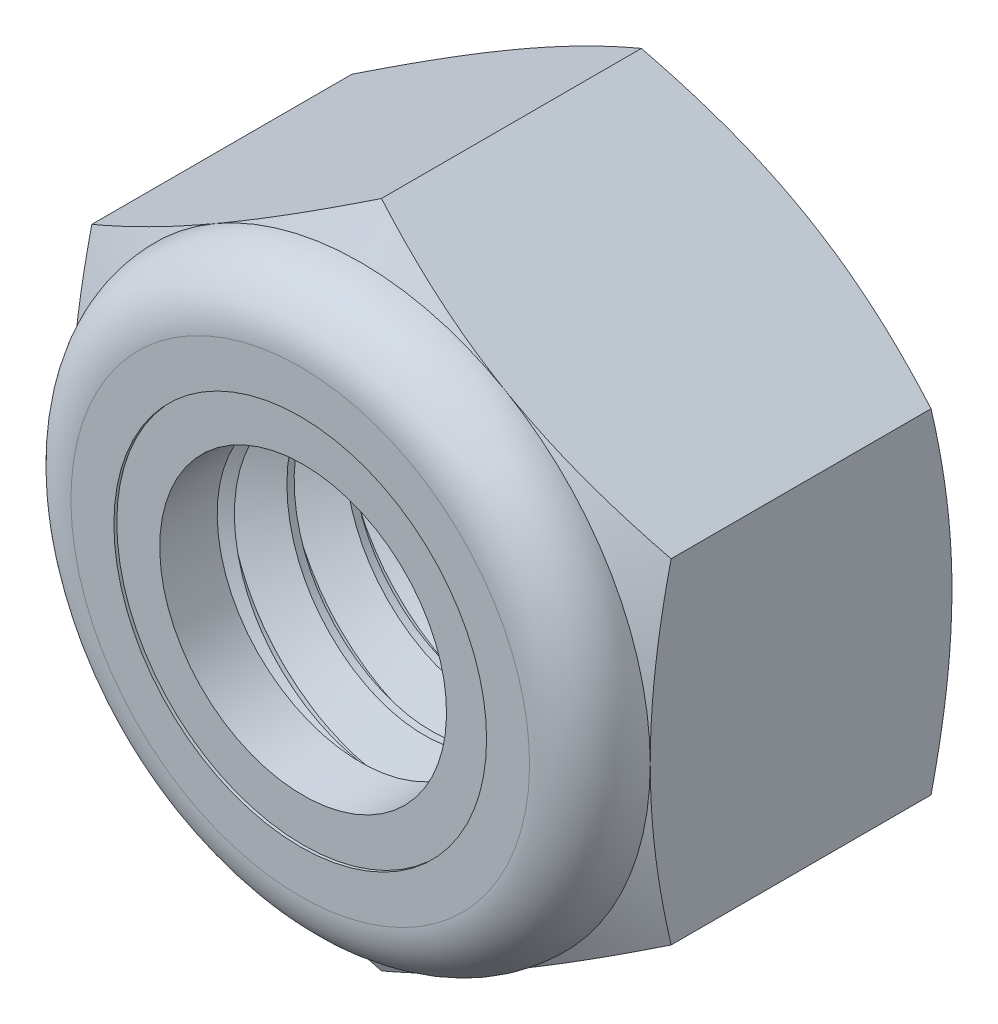
SolidWorks part; units mm, degrees
material "Cast Alloy Steel"
ref_plane "Front Plane" through (0, 0, 0) normal (0, 0, 1) x (1, 0, 0)
ref_plane "Top Plane" through (0, 0, 0) normal (0, 1, 0) x (1, 0, 0)
ref_plane "Right Plane" through (0, 0, 0) normal (1, 0, 0) x (0, 0, -1)
sketch "Sketch1" plane through (0, 0, 0) normal (0, 0, 1) x (1, 0, 0)
  line L1 (0, 4.6188) -> (-4, 2.3094)
  line L2 (-4, 2.3094) -> (-4, -2.3094)
  line L3 (-4, -2.3094) -> (0, -4.6188)
  line L4 (0, -4.6188) -> (4, -2.3094)
  line L5 (4, -2.3094) -> (4, 2.3094)
  line L6 (4, 2.3094) -> (0, 4.6188)
  circle A0 centre (0, 0) radius 4 construction
  circle A1 centre (0, 0) radius 2.5
  point P10 (0, -2.5)
  point P11 (0, 2.5)
  point P12 (0, 4)
  dimension "Thread Size" = 5
  dimension "Width" = 8
sketch "Sketch2" plane through (0, 0, 0) normal (1, 0, 0) x (0, 0, -1)
  line L0 (2.5, 0) -> (-2.5, 0) construction
  line L1 (-2.5, 2.5) -> (2.5, 2.5) construction
  line L2 (-2.46, -2.5735) -> (-3.77, -2.5735) construction
  line L3 (-3.25, 2.5866) -> (-2.45, 2.5866) construction
  line L4 (-2.45, 2.5866) -> (-2.85, 1.8938) construction
  line L5 (-2.85, 1.8938) -> (-3.25, 2.5866) construction
  line L6 (-3.2, 2.5) -> (-2.5, 2.5) construction
  line L7 (-2.9, 1.9804) -> (-2.8, 1.9804) construction
  line L8 (-2.85, 1.9804) -> (-2.85, 1.8938) construction
  line L9 (-2.85, 2.5) -> (-2.85, 2.5866) construction
  line L10 (-2.475, 2.5433) -> (-3.225, 2.5433)
  line L11 (-3.225, 2.5433) -> (-2.9, 1.9804)
  line L12 (-2.9, 1.9804) -> (-2.8, 1.9804)
  line L13 (-2.8, 1.9804) -> (-2.475, 2.5433)
  line L14 (2.5, 0) -> (3.77, 0)
  line L15 (3.77, 0) -> (3.77, 5.8888)
  line L16 (0, 5.8888) -> (0, 4.6188) construction
  line L17 (0, 4.6188) -> (0, 2.3094) construction
  line L18 (2.5, 4) -> (-1.6667, 4) construction
  line L19 (-2.9, -1.9804) -> (-2.8, -1.9804) construction
  line L20 (2.5, 4) -> (2.5, 0)
  line L21 (2.2114, 4.6188) -> (-1.3781, 4.6188)
  line L22 (2.5, 4) -> (2.2114, 4.6188)
  line L23 (-2.5, 0) -> (-2.5, 3.1667) construction
  line L24 (-1.6667, 4) -> (-1.3781, 4.6188)
  line L25 (3.77, 5.8888) -> (-3.77, 5.8888)
  line L26 (-2.5, 3.1667) -> (-3.77, 3.1667)
  line L27 (-3.77, 3.1667) -> (-3.77, 5.8888)
  line L28 (-2.46, 3.1667) -> (-2.46, 1.9804) construction
  line L29 (-2.46, 2.5735) -> (-3.77, 2.5735)
  line L30 (-3.77, 2.5735) -> (-3.77, 0)
  line L31 (-3.77, 0) -> (-1.6667, 0)
  line L32 (-1.6667, 0) -> (-1.6667, 3.96)
  line L33 (-2.46, 2.5735) -> (-2.46, 3.1667)
  arc A0 (-1.6667, 4) -> (-2.5, 3.1667) centre (-1.6667, 3.1667) ccw
  arc A1 (-1.6667, 3.96) -> (-2.46, 3.1667) centre (-1.6667, 3.1667) ccw
  point P4 (0, 0)
  point P18 (-2.85, 2.5433)
  point P22 (-2.85, 2.5433)
  point P33 (0, 4.6188)
  point P48 (-3.77, -2.5735)
  point P51 (-2.9, -1.9804)
  dimension "Height" = 5
  dimension "Pitch" = 0.8
  dimension "D1" = 0.1
  dimension "D2" = 1.27
  dimension "D3" = 25
  dimension "D4" = 0.8333
  dimension "D5" = 25
  dimension "D6" = 0.04
sketch "Sketch3" plane through (0, 0, 0) normal (0, 0, 1) x (1, 0, 0)
  line L0 (0, -4.6188) -> (4, -2.3094) construction
  line L1 (4, -2.3094) -> (4, 2.3094) construction
  line L2 (4, 2.3094) -> (0, 4.6188) construction
  line L3 (0, 4.6188) -> (-4, 2.3094) construction
  line L4 (-4, 2.3094) -> (-4, -2.3094) construction
  line L5 (-4, -2.3094) -> (0, -4.6188) construction
  line L6 (0, -4.6188) -> (4, -2.3094)
  line L7 (4, -2.3094) -> (4, 2.3094)
  line L8 (4, 2.3094) -> (0, 4.6188)
  line L9 (0, 4.6188) -> (-4, 2.3094)
  line L10 (-4, 2.3094) -> (-4, -2.3094)
  line L11 (-4, -2.3094) -> (0, -4.6188)
  circle A0 centre (0, 0) radius 2.5 construction
  circle A1 centre (0, 0) radius 2.5
extrude "Boss-Extrude1" add sketch "Sketch3" along normal mid plane 5
sketch "Sketch4" plane through (0, 0, 0) normal (1, 0, 0) x (0, 0, -1)
  line L0 (3.77, 5.8888) -> (-3.77, 5.8888) construction
  line L1 (-3.77, 3.1667) -> (-3.77, 5.8888) construction
  line L2 (-2.5, 3.1667) -> (-3.77, 3.1667) construction
  line L3 (-1.6667, 4) -> (-1.3781, 4.6188) construction
  line L4 (2.2114, 4.6188) -> (-1.3781, 4.6188) construction
  line L5 (2.5, 4) -> (2.2114, 4.6188) construction
  line L6 (2.5, 4) -> (2.5, 0) construction
  line L7 (2.5, 0) -> (3.77, 0) construction
  line L8 (3.77, 0) -> (3.77, 5.8888) construction
  line L9 (-3.77, 2.5735) -> (-3.77, 0) construction
  line L10 (-3.77, 0) -> (-1.6667, 0) construction
  line L11 (-1.6667, 0) -> (-1.6667, 3.96) construction
  line L12 (-2.46, 2.5735) -> (-2.46, 3.1667) construction
  line L13 (-2.46, 2.5735) -> (-3.77, 2.5735) construction
  line L14 (3.77, 5.8888) -> (-3.77, 5.8888)
  line L15 (-3.77, 3.1667) -> (-3.77, 5.8888)
  line L16 (-2.5, 3.1667) -> (-3.77, 3.1667)
  line L17 (-1.6667, 4) -> (-1.3781, 4.6188)
  line L18 (2.2114, 4.6188) -> (-1.3781, 4.6188)
  line L19 (2.5, 4) -> (2.2114, 4.6188)
  line L20 (2.5, 4) -> (2.5, 0)
  line L21 (2.5, 0) -> (3.77, 0)
  line L22 (3.77, 0) -> (3.77, 5.8888)
  line L23 (-3.77, 2.5735) -> (-3.77, 0)
  line L24 (-3.77, 0) -> (-1.6667, 0)
  line L25 (-1.6667, 0) -> (-1.6667, 3.96)
  line L26 (-2.46, 2.5735) -> (-2.46, 3.1667)
  line L27 (-2.46, 2.5735) -> (-3.77, 2.5735)
  arc A0 (-1.6667, 4) -> (-2.5, 3.1667) centre (-1.6667, 3.1667) ccw construction
  arc A1 (-1.6667, 3.96) -> (-2.46, 3.1667) centre (-1.6667, 3.1667) ccw construction
  arc A2 (-1.6667, 4) -> (-2.5, 3.1667) centre (-1.6667, 3.1667) ccw
  arc A3 (-1.6667, 3.96) -> (-2.46, 3.1667) centre (-1.6667, 3.1667) ccw
revolve "Cut-Revolve1" cut sketch "Sketch4" angle 360 about L0
sketch "Sketch5" plane through (0, 0, 0) normal (1, 0, 0) x (0, 0, -1)
  line L0 (-2.46, 3.1667) -> (-2.46, 1.9804) construction
  line L1 (-1.6667, 0) -> (-1.6667, 3.96) construction
  line L2 (-2.46, 3.1667) -> (-2.46, 1.9804)
  line L3 (-1.6667, 1.9804) -> (-1.6667, 3.96)
  line L4 (-2.46, 1.9804) -> (-1.6667, 1.9804)
  arc A0 (-1.6667, 3.96) -> (-2.46, 3.1667) centre (-1.6667, 3.1667) ccw construction
  arc A1 (-1.6667, 3.96) -> (-2.46, 3.1667) centre (-1.6667, 3.1667) ccw
revolve "Revolve1" add sketch "Sketch5" angle 360 about L0
sketch "Sketch6" plane through (0, 0, 2.5) normal (0, 0, 1) x (1, 0, 0)
  circle A0 centre (0, 0) radius 2.5 construction
  circle A1 centre (0, 0) radius 2.5
curve "Helix/Spiral1" pitch 0.8 height 5.8 radius 2.5 centre (0, 0, 2.5) axis (0, 0, -1) start towards (0, 1, 0)
sketch "Sketch7" plane through (0, 0, 0) normal (1, 0, 0) x (0, 0, -1)
  line L0 (-3.225, 2.5433) -> (-2.9, 1.9804) construction
  line L1 (-2.9, 1.9804) -> (-2.8, 1.9804) construction
  line L2 (-2.8, 1.9804) -> (-2.475, 2.5433) construction
  line L3 (-2.475, 2.5433) -> (-3.225, 2.5433) construction
  line L4 (-3.225, 2.5433) -> (-2.9, 1.9804)
  line L5 (-2.9, 1.9804) -> (-2.8, 1.9804)
  line L6 (-2.8, 1.9804) -> (-2.475, 2.5433)
  line L7 (-2.475, 2.5433) -> (-3.225, 2.5433)
sweep "Sweep1" add profiles "Sketch7" path "Helix/Spiral1"
sketch "Sketch8" plane through (0, 0, -2.5) normal (0, 0, -1) x (-1, 0, 0)
  circle A2 centre (0, 0) radius 2.5433
  point P2 (0, 2.5433)
extrude "Cut-Extrude1" cut sketch "Sketch8" along normal through all and the other way through all draft 60
sketch "Sketch9" plane through (0, 0, 1.6667) normal (0, 0, 1) x (1, 0, 0)
  circle A2 centre (0, 0) radius 2.5433
  circle A3 centre (0, 0) radius 1.9804 construction
  point P2 (0, 2.5433)
  point P4 (0, 1.9804)
extrude "Cut-Extrude2" cut sketch "Sketch9" along normal through all and the other way through all draft 60
equation "\"D1@Sketch2\" = \"Pitch@Sketch2\" / 8"
equation "\"D4@Sketch2\"=\"Height@Sketch2\"/6"
equation "\"D1@Boss-Extrude1\"=\"Height@Sketch2\""
equation "\"D3@Helix/Spiral1\"=\"Height@Sketch2\"+\"Pitch@Sketch2\""
equation "\"D4@Helix/Spiral1\"=\"Pitch@Sketch2\""
equation "\"D6@Sketch2\"=\"Pitch@Sketch2\"*0.05"
